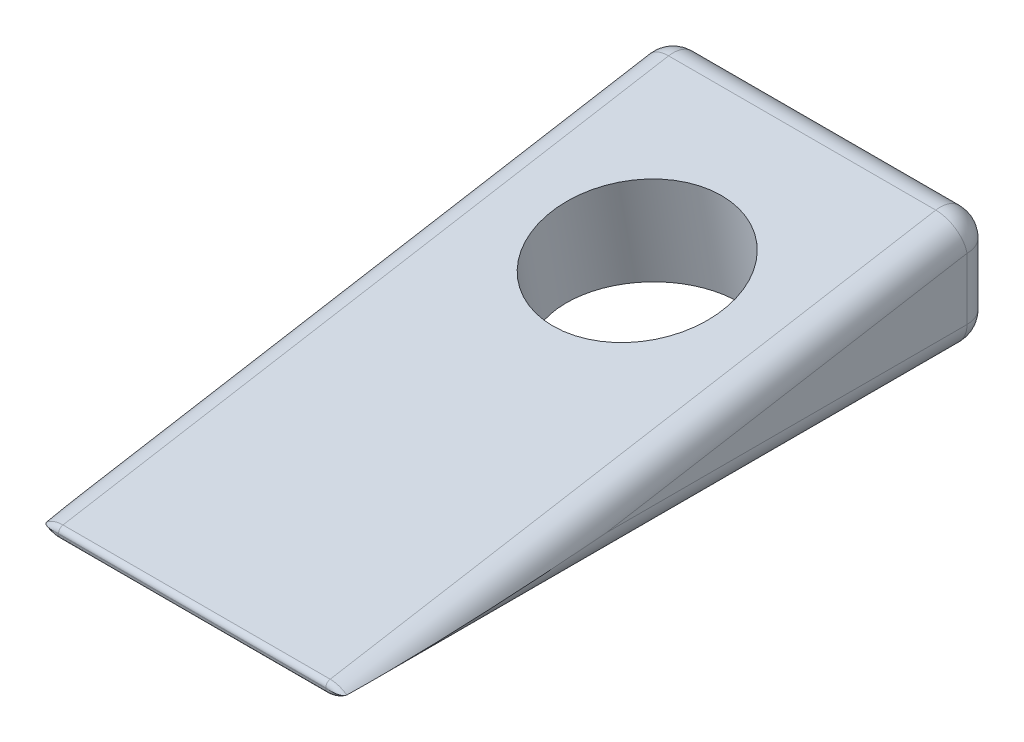
SolidWorks part; units mm, degrees
ref_plane "Front Plane" through (0, 0, 0) normal (0, 0, 1) x (1, 0, 0)
ref_plane "Top Plane" through (0, 0, 0) normal (0, 1, 0) x (1, 0, 0)
ref_plane "Right Plane" through (0, 0, 0) normal (1, 0, 0) x (0, 0, -1)
sketch "Sketch1" plane through (0, 0, 0) normal (0, 1, 0) x (1, 0, 0)
  line L1 (-4.7625, -9.525) -> (4.7625, -9.525)
  line L2 (-4.7625, -9.525) -> (-4.7625, 9.525)
  line L3 (-4.7625, 9.525) -> (4.7625, 9.525)
  line L4 (4.7625, -9.525) -> (4.7625, 9.525)
  line L5 (-4.7625, -9.525) -> (4.7625, 9.525) construction
  line L6 (-4.7625, 9.525) -> (4.7625, -9.525) construction
  point P0 (0, 0)
  dimension "D1" = 19.05
  dimension "D2" = 9.525
extrude "Boss-Extrude1" add sketch "Sketch1" along normal blind 6.35
sketch "Sketch4" plane through (-4.7625, 0, 0) normal (-1, 0, 0) x (0, 0, 1)
  line L1 (9.525, 6.35) -> (9.525, 0) construction
  line L2 (-59.4387, 12.0907) -> (46.9704, -6.0836) construction
  line L3 (9.525, 0.3119) -> (-9.525, 3.5656)
  line L4 (-9.525, 6.35) -> (-9.525, 0) construction
  line L7 (9.525, 0.3119) -> (9.525, 6.35)
  line L8 (9.525, 6.35) -> (-9.525, 6.35)
  line L9 (-9.525, 6.35) -> (-9.525, 3.5656)
extrude "Cut-Extrude4" cut sketch "Sketch4" against normal through all both and the other way through all
sketch "Sketch7" plane through (0, 1.9111, 0.162) normal (0, -0.9857, -0.1684) x (1, 0, 0)
  circle A0 centre (0, -3.9144) radius 2.54
  ellipse E0 centre (0, -3.9144) end of major axis (-2.1, -3.9144) minor radius 2.07 (-2.1, -3.9144) -> (2.1, -3.9144) ccw construction
  dimension "D2" = 5.08
extrude "Cut-Extrude6" cut sketch "Sketch7" against normal through all both and the other way through all
fillet "Fillet2" radius 0.7937 8 edges at (4.7625, 0, 0) (4.7625, 1.9388, 0) (0, 0, -9.525) (4.7625, 1.7828, -9.525) (0, 3.5656, -9.525) (-4.7625, 0, 0) (-4.7625, 1.7828, -9.525) (-4.7625, 1.9388, 0)
fillet "Fillet3" radius 0.1588 6 edges at (-4.2166, 0.0397, 9.525) (4.2166, 0.0397, 9.525) (4.2166, 0.2716, 9.525) (-4.2166, 0.2716, 9.525) (0, 0, 9.525) (0, 0.3119, 9.525)
